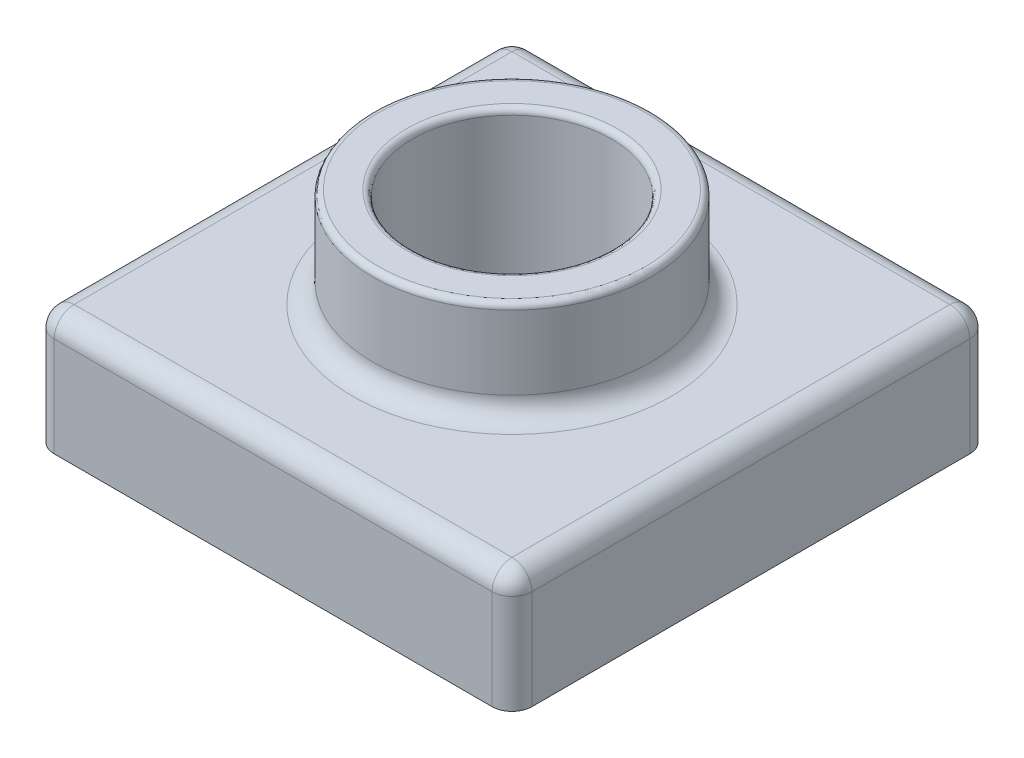
SolidWorks part; units mm, degrees
ref_plane "Front Plane" through (0, 0, 0) normal (0, 0, 1) x (1, 0, 0)
ref_plane "Top Plane" through (0, 0, 0) normal (0, 1, 0) x (1, 0, 0)
ref_plane "Right Plane" through (0, 0, 0) normal (1, 0, 0) x (0, 0, -1)
sketch "Sketch1" plane through (0, 0, 0) normal (0, 1, 0) x (1, 0, 0)
  line L1 (0, 0) -> (3048, 0)
  line L2 (0, 0) -> (0, 3048)
  line L3 (0, 3048) -> (3048, 3048)
  line L4 (3048, 0) -> (3048, 3048)
  dimension "D1" = 3048
  dimension "D2" = 3048
extrude "Boss-Extrude1" add sketch "Sketch1" along normal blind 762
sketch "Sketch2" plane through (0, 762, 0) normal (0, 1, 0) x (1, 0, 0)
  line L0 (0, 3048) -> (3048, 0) construction
  circle A0 centre (1524, 1524) radius 889
  dimension "D1" = 1778
extrude "Boss-Extrude2" add sketch "Sketch2" along normal blind 635
sketch3d "3DSketch1"
  spline S0 degree 3 poles (1484.734, 1397, -889.8102) (1526.8789, 1397, -888.5057) (1571.9096, 1397, -890.2062) (1619.5462, 1397, -895.6198) (1666.6392, 1397, -904.6092) (1712.9219, 1397, -917.1242) (1768.1583, 1397, -936.6309) (1830.9094, 1397, -966.1802) (1898.4388, 1397, -1009.071) (1951.8609, 1397, -1053.3082) (1992.9985, 1397, -1095.0127) (2024.0014, 1397, -1131.5851) (2052.1574, 1397, -1170.3894) (2077.3086, 1397, -1211.2068) (2101.1441, 1397, -1257.3478) (2122.5195, 1397, -1309.0663) (2140.0995, 1397, -1366.3834) (2152.2047, 1397, -1425.1022) (2158.7266, 1397, -1484.6997) (2159.6065, 1397, -1544.6467) (2154.8374, 1397, -1604.4101) (2144.462, 1397, -1663.4588) (2128.5723, 1397, -1721.2682) (2107.3085, 1397, -1777.3241) (2080.8606, 1397, -1831.1285) (2049.4638, 1397, -1882.2034) (2013.3969, 1397, -1930.0949) (1972.9798, 1397, -1974.3766) (1928.5724, 1397, -2014.6555) (1880.5696, 1397, -2050.5739) (1829.3976, 1397, -2081.8124) (1775.511, 1397, -2108.0926) (1719.3892, 1397, -2129.1815) (1661.5309, 1397, -2144.8922) (1602.4503, 1397, -2155.0848) (1542.6723, 1397, -2159.6676) (1482.7284, 1397, -2158.6009) (1423.1513, 1397, -2151.8945) (1364.4705, 1397, -2139.6076) (1307.2076, 1397, -2121.8486) (1251.8717, 1397, -2098.7763) (1198.9541, 1397, -2070.5959) (1148.9253, 1397, -2037.5576) (1102.2305, 1397, -1999.9542) (1059.2843, 1397, -1958.1209) (1020.468, 1397, -1912.4295) (986.1269, 1397, -1863.2859) (956.5669, 1397, -1811.1264) (932.0499, 1397, -1756.415) (912.7937, 1397, -1699.6383) (898.9696, 1397, -1641.3004) (890.7013, 1397, -1581.9199) (888.0616, 1397, -1522.0245) (891.0732, 1397, -1462.1477) (899.1354, 1397, -1406.7698) (910.9484, 1397, -1356.1973) (925.3405, 1397, -1310.4642) (943.1388, 1397, -1265.9474) (964.2438, 1397, -1222.8974) (993.9186, 1397, -1172.3903) (1034.8839, 1397, -1116.4197) (1089.8567, 1397, -1058.3006) (1143.4632, 1397, -1014.2869) (1192.2424, 1397, -981.85) (1234.0524, 1397, -958.3842) (1277.5111, 1397, -938.1383) (1322.3723, 1397, -921.2261) (1365.6168, 1397, -908.5521) (1406.7996, 1397, -899.4985) (1445.6172, 1397, -893.4479) (1484.734, 1397, -889.8102) (1526.8789, 1397, -888.5057) (1571.9096, 1397, -890.2062) knots -0.029531 -0.019687 -0.009844 0 0.012009 0.024019 0.036028 0.048038 0.060047 0.080055 0.100062 0.120069 0.132079 0.144088 0.156097 0.168107 0.180116 0.195126 0.210136 0.225146 0.240156 0.255165 0.270175 0.285185 0.300195 0.315205 0.330214 0.345224 0.360234 0.375244 0.390254 0.405263 0.420273 0.435283 0.450293 0.465303 0.480312 0.495322 0.510332 0.525342 0.540352 0.555361 0.570371 0.585381 0.600391 0.615401 0.63041 0.64542 0.66043 0.67544 0.69045 0.705459 0.720469 0.735479 0.750489 0.765499 0.780508 0.792518 0.804527 0.816537 0.828546 0.840556 0.860563 0.88057 0.900577 0.912587 0.924596 0.936606 0.948615 0.960625 0.970469 0.980313 0.990156 1 1.012009 1.024019 1.036028 only from (1524, 1397, -889) to (1524, 1397, -889)
  spline S1 degree 3 poles (1484.734, 1397, -889.8102) (1526.8789, 1397, -888.5057) (1571.9096, 1397, -890.2062) (1619.5462, 1397, -895.6198) (1666.6392, 1397, -904.6092) (1712.9219, 1397, -917.1242) (1768.1583, 1397, -936.6309) (1830.9094, 1397, -966.1802) (1898.4388, 1397, -1009.071) (1951.8609, 1397, -1053.3082) (1992.9985, 1397, -1095.0127) (2024.0014, 1397, -1131.5851) (2052.1574, 1397, -1170.3894) (2077.3086, 1397, -1211.2068) (2101.1441, 1397, -1257.3478) (2122.5195, 1397, -1309.0663) (2140.0995, 1397, -1366.3834) (2152.2047, 1397, -1425.1022) (2158.7266, 1397, -1484.6997) (2159.6065, 1397, -1544.6467) (2154.8374, 1397, -1604.4101) (2144.462, 1397, -1663.4588) (2128.5723, 1397, -1721.2682) (2107.3085, 1397, -1777.3241) (2080.8606, 1397, -1831.1285) (2049.4638, 1397, -1882.2034) (2013.3969, 1397, -1930.0949) (1972.9798, 1397, -1974.3766) (1928.5724, 1397, -2014.6555) (1880.5696, 1397, -2050.5739) (1829.3976, 1397, -2081.8124) (1775.511, 1397, -2108.0926) (1719.3892, 1397, -2129.1815) (1661.5309, 1397, -2144.8922) (1602.4503, 1397, -2155.0848) (1542.6723, 1397, -2159.6676) (1482.7284, 1397, -2158.6009) (1423.1513, 1397, -2151.8945) (1364.4705, 1397, -2139.6076) (1307.2076, 1397, -2121.8486) (1251.8717, 1397, -2098.7763) (1198.9541, 1397, -2070.5959) (1148.9253, 1397, -2037.5576) (1102.2305, 1397, -1999.9542) (1059.2843, 1397, -1958.1209) (1020.468, 1397, -1912.4295) (986.1269, 1397, -1863.2859) (956.5669, 1397, -1811.1264) (932.0499, 1397, -1756.415) (912.7937, 1397, -1699.6383) (898.9696, 1397, -1641.3004) (890.7013, 1397, -1581.9199) (888.0616, 1397, -1522.0245) (891.0732, 1397, -1462.1477) (899.1354, 1397, -1406.7698) (910.9484, 1397, -1356.1973) (925.3405, 1397, -1310.4642) (943.1388, 1397, -1265.9474) (964.2438, 1397, -1222.8974) (993.9186, 1397, -1172.3903) (1034.8839, 1397, -1116.4197) (1089.8567, 1397, -1058.3006) (1143.4632, 1397, -1014.2869) (1192.2424, 1397, -981.85) (1234.0524, 1397, -958.3842) (1277.5111, 1397, -938.1383) (1322.3723, 1397, -921.2261) (1365.6168, 1397, -908.5521) (1406.7996, 1397, -899.4985) (1445.6172, 1397, -893.4479) (1484.734, 1397, -889.8102) (1526.8789, 1397, -888.5057) (1571.9096, 1397, -890.2062) knots -0.029531 -0.019687 -0.009844 0 0.012009 0.024019 0.036028 0.048038 0.060047 0.080055 0.100062 0.120069 0.132079 0.144088 0.156097 0.168107 0.180116 0.195126 0.210136 0.225146 0.240156 0.255165 0.270175 0.285185 0.300195 0.315205 0.330214 0.345224 0.360234 0.375244 0.390254 0.405263 0.420273 0.435283 0.450293 0.465303 0.480312 0.495322 0.510332 0.525342 0.540352 0.555361 0.570371 0.585381 0.600391 0.615401 0.63041 0.64542 0.66043 0.67544 0.69045 0.705459 0.720469 0.735479 0.750489 0.765499 0.780508 0.792518 0.804527 0.816537 0.828546 0.840556 0.860563 0.88057 0.900577 0.912587 0.924596 0.936606 0.948615 0.960625 0.970469 0.980313 0.990156 1 1.012009 1.024019 1.036028 only from (1524, 1397, -889) to (1524, 1397, -889)
  dimension "D1" = 254
extrude "Cut-Extrude2" cut sketch "3DSketch1" along direction (0, 1, 0) on the side against the normal through all
fillet "Fillet1" radius 127 9 edges at (1524, 762, -3048) (3048, 762, -1524) (1524, 762, 0) (0, 762, -1524) (1524, 762, -635) (0, 381, -3048) (0, 381, 0) (3048, 381, 0) (3048, 381, -3048)
fillet "Fillet2" radius 38.1 2 edges at (1524, 1397, -635)
shell "Shell1" thickness 2
